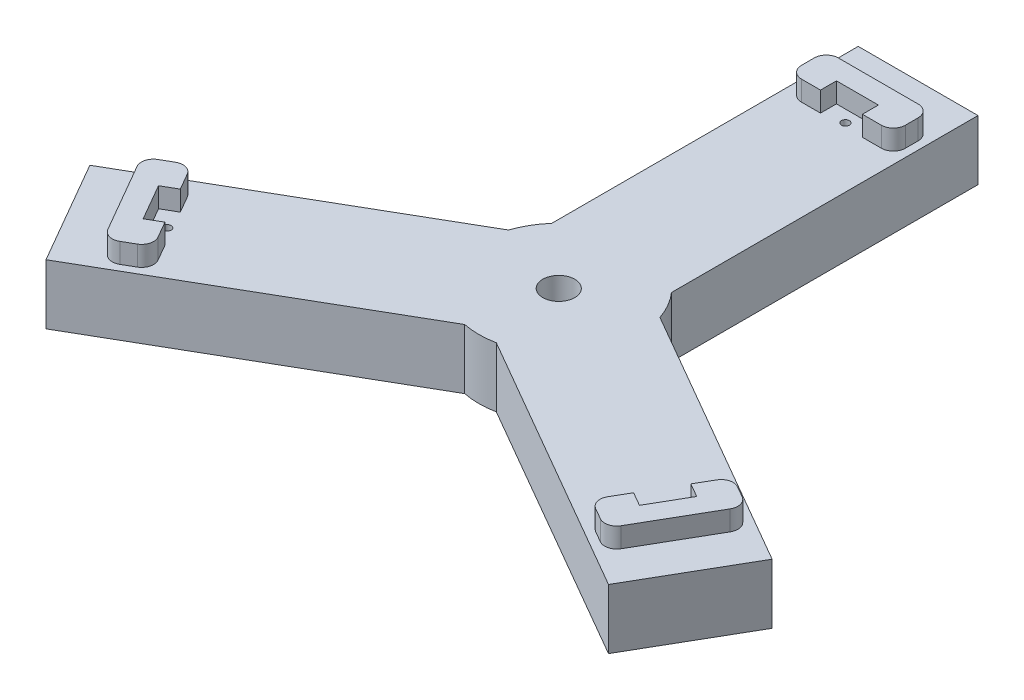
SolidWorks part; units mm, degrees
ref_plane "Front Plane" through (0, 0, 0) normal (0, 0, 1) x (1, 0, 0)
ref_plane "Top Plane" through (0, 0, 0) normal (0, 1, 0) x (1, 0, 0)
ref_plane "Right Plane" through (0, 0, 0) normal (1, 0, 0) x (0, 0, -1)
sketch "Sketch5" plane through (0, 0, 0) normal (0, 1, 0) x (1, 0, 0)
  circle A0 centre (0, 0) radius 20
  dimension "D1" = 40
extrude "Boss-Extrude2" add sketch "Sketch5" along normal blind 15
sketch "Sketch6" plane through (0, 0, 0) normal (0, 1, 0) x (1, 0, 0)
  line L0 (0, -11) -> (0, 11) construction
  line L1 (15, 0) -> (-15, 0)
  line L2 (15, 0) -> (15, 90)
  line L3 (15, 90) -> (-15, 90)
  line L4 (-15, 0) -> (-15, 90)
  dimension "D1" = 90
  dimension "D2" = 15
  dimension "D3" = 15
extrude "Boss-Extrude3" add sketch "Sketch6" along normal blind 15
pattern_circular "CirPattern1" count 3 over 360 about axis through (0, 15, 0) along (0, -1, 0) of "Boss-Extrude3"
sketch "Sketch7" plane through (0, 15, 0) normal (0, 1, 0) x (1, 0, 0)
  line L0 (0, -11) -> (0, 11) construction
  line L1 (-13, 80) -> (13, 80)
  line L2 (-13, 80) -> (-13, 70.8)
  line L3 (-13, 70.8) -> (-5.25, 70.8)
  line L4 (13, 80) -> (13, 70.8)
  line L5 (5.25, 70.8) -> (5.25, 74.8)
  line L6 (5.25, 74.8) -> (-5.25, 74.8)
  line L7 (-5.25, 74.8) -> (-5.25, 70.8)
  line L8 (-11, 0) -> (11, 0) construction
  line L9 (5.25, 70.8) -> (13, 70.8)
  point P8 (5.25, 72.8)
  dimension "D1" = 26
  dimension "D2" = 13
  dimension "D3" = 9.2
  dimension "D4" = 5.25
  dimension "D5" = 4
  dimension "D6" = 5.25
  dimension "D7" = 80
extrude "Boss-Extrude4" add sketch "Sketch7" along normal blind 5
fillet "Fillet1" radius 3 4 edges at (13, 17.5, -70.8) (13, 17.5, -80) (-13, 17.5, -70.8) (-13, 17.5, -80)
sketch "Sketch8" plane through (0, 15, 0) normal (0, 1, 0) x (1, 0, 0)
  line L0 (5.25, 70.8) -> (10, 70.8) construction
  circle A0 centre (0, 71.8) radius 1
  dimension "D1" = 2
  dimension "D2" = 1
extrude "Cut-Extrude1" cut sketch "Sketch8" against normal through all
sketch "Sketch9" plane through (0, 0, 0) normal (0, -1, 0) x (1, 0, 0)
  circle A0 centre (0, -71.8) radius 10
  dimension "D1" = 20
extrude "Cut-Extrude2" cut sketch "Sketch9" against normal blind 10 contours A0
pattern_circular "CirPattern4" count 3 over 360 about axis through (0, 15, 0) along (0, -1, 0) of "Boss-Extrude4", "Fillet1"
pattern_circular "CirPattern6" count 3 over 360 about axis through (0, 15, 0) along (0, -1, 0) of "Cut-Extrude1", "Cut-Extrude2"
sketch "Sketch10" plane through (0, 0, 0) normal (0, -1, 0) x (1, 0, 0)
  circle A0 centre (0, 0) radius 11
  dimension "D1" = 22
extrude "Cut-Extrude3" cut sketch "Sketch10" against normal blind 4
sketch "Sketch11" plane through (0, 0, 0) normal (0, 1, 0) x (1, 0, 0)
  circle A0 centre (0, 0) radius 4
  dimension "D1" = 8
extrude "Cut-Extrude4" cut sketch "Sketch11" along normal up to next
